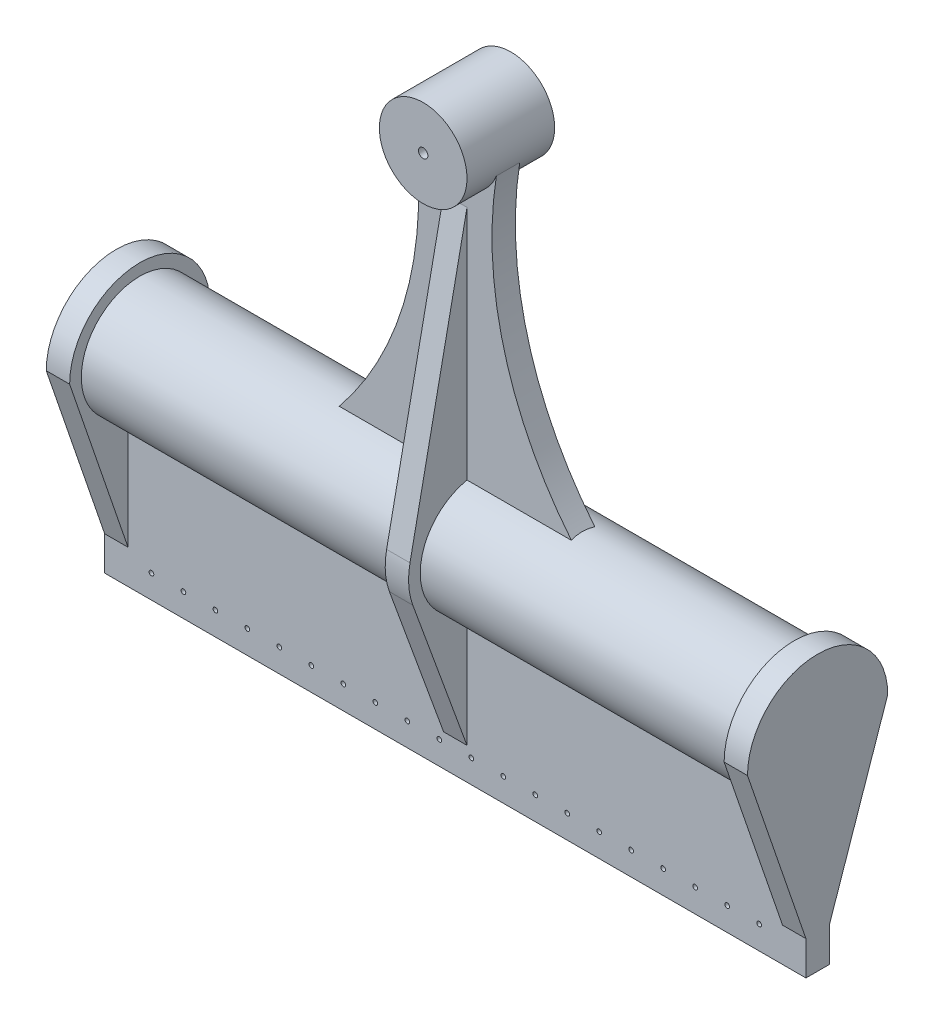
SolidWorks part; units mm, degrees
ref_plane "Front Plane" through (0, 0, 0) normal (1, 0, 0) x (0, 1, 0)
ref_plane "Top Plane" through (0, 0, 0) normal (0, 0, 1) x (0, 1, 0)
ref_plane "Right Plane" through (0, 0, 0) normal (0, 1, 0) x (-1, 0, 0)
sketch "Sketch1" plane through (0, 0, 0) normal (0, 0, 1) x (0, 1, 0)
  line L1 (-44.45, -76.2) -> (0, -76.2)
  line L2 (-44.45, -76.2) -> (-44.45, 76.2)
  line L3 (-44.45, 76.2) -> (0, 76.2)
  line L4 (0, -76.2) -> (0, 76.2)
  line L5 (-44.45, -76.2) -> (0, 76.2) construction
  line L6 (-44.45, 76.2) -> (0, -76.2) construction
  circle A0 centre (-39.37, -66.04) radius 0.508
  circle A1 centre (-39.37, -59.0884) radius 0.508
  circle A2 centre (-39.37, -52.1368) radius 0.508
  circle A3 centre (-39.37, -45.1853) radius 0.508
  circle A4 centre (-39.37, -38.2337) radius 0.508
  circle A5 centre (-39.37, -31.2821) radius 0.508
  circle A6 centre (-39.37, -24.3305) radius 0.508
  circle A7 centre (-39.37, -17.3789) radius 0.508
  circle A8 centre (-39.37, -10.4274) radius 0.508
  circle A9 centre (-39.37, -3.4758) radius 0.508
  circle A10 centre (-39.37, 3.4758) radius 0.508
  circle A11 centre (-39.37, 10.4274) radius 0.508
  circle A12 centre (-39.37, 17.3789) radius 0.508
  circle A13 centre (-39.37, 24.3305) radius 0.508
  circle A14 centre (-39.37, 31.2821) radius 0.508
  circle A15 centre (-39.37, 38.2337) radius 0.508
  circle A16 centre (-39.37, 45.1853) radius 0.508
  circle A17 centre (-39.37, 52.1368) radius 0.508
  circle A18 centre (-39.37, 59.0884) radius 0.508
  circle A19 centre (-39.37, 66.04) radius 0.508
  point P0 (-22.225, 0)
extrude "Boss-Extrude1" add sketch "Sketch1" along normal blind 2.54 and the other way blind 2.54
sketch "Sketch2" plane through (0, 0, 0) normal (1, 0, 0) x (0, 1, 0)
  circle A0 centre (0, 0) radius 12.7
extrude "Boss-Extrude2" add sketch "Sketch2" along normal blind 76.2 and the other way blind 76.2
sketch "Sketch3" plane through (0, 0, 0) normal (1, 0, 0) x (0, 1, 0)
  line L0 (0, 15.24) -> (-44.45, 0)
  line L1 (-44.45, 0) -> (0, -15.24)
  arc A0 (0, -15.24) -> (0, 15.24) centre (0, 0) ccw
extrude "Boss-Extrude3" add sketch "Sketch3" along normal blind 5.08 from offset 71.12
sketch "Sketch4" plane through (0, 0, 0) normal (1, 0, 0) x (0, 1, 0)
  line L0 (0, 15.24) -> (-44.45, 0)
  line L1 (-44.45, 0) -> (0, -15.24)
  arc A0 (0, -15.24) -> (0, 15.24) centre (0, 0) ccw
extrude "Boss-Extrude4" add sketch "Sketch4" against normal blind 5.08 from offset 71.12 offset against normal yes
sketch "Sketch5" plane through (0, 0, 0) normal (0, 0, 1) x (0, 1, 0)
  line L0 (0, -38.1) -> (0, 38.1)
  line L1 (76.2, 9.525) -> (76.2, -9.525)
  arc A0 (0, 38.1) -> (76.2, 9.525) centre (60.8501, 84.4794) ccw
  arc A1 (76.2, -9.525) -> (0, -38.1) centre (60.8501, -84.4794) ccw
extrude "Boss-Extrude5" add sketch "Sketch5" along normal blind 2.54 and the other way blind 2.54
sketch "Sketch6" plane through (0, 0, 0) normal (0, 0, 1) x (0, 1, 0)
  circle A0 centre (76.2, 0) radius 9.525
  circle A1 centre (76.2, 0) radius 1.016
extrude "Boss-Extrude6" add sketch "Sketch6" along normal blind 9.525 and the other way blind 9.525
sketch "Sketch7" plane through (0, 0, 0) normal (1, 0, 0) x (0, 1, 0)
  line L0 (-44.45, 0) -> (-5.225, 14.3163)
  line L1 (-44.45, -2.54) -> (-44.45, 2.54) construction
  line L2 (3.0481, 14.9321) -> (76.2, 0)
  line L3 (76.2, 0) -> (3.0481, -14.9321)
  line L4 (-5.225, -14.3163) -> (-44.45, 0)
  line L5 (-44.45, 0) -> (76.2, 0) construction
  arc A0 (-5.225, 14.3163) -> (3.0481, 14.9321) centre (0.0001, 0) cw
  arc A1 (0, -15.24) -> (0, 15.24) centre (0, 0) ccw construction
  arc A2 (3.0481, -14.9321) -> (-5.225, -14.3163) centre (0.0001, 0) cw
extrude "Boss-Extrude7" add sketch "Sketch7" along normal blind 2.54 and the other way blind 2.54
